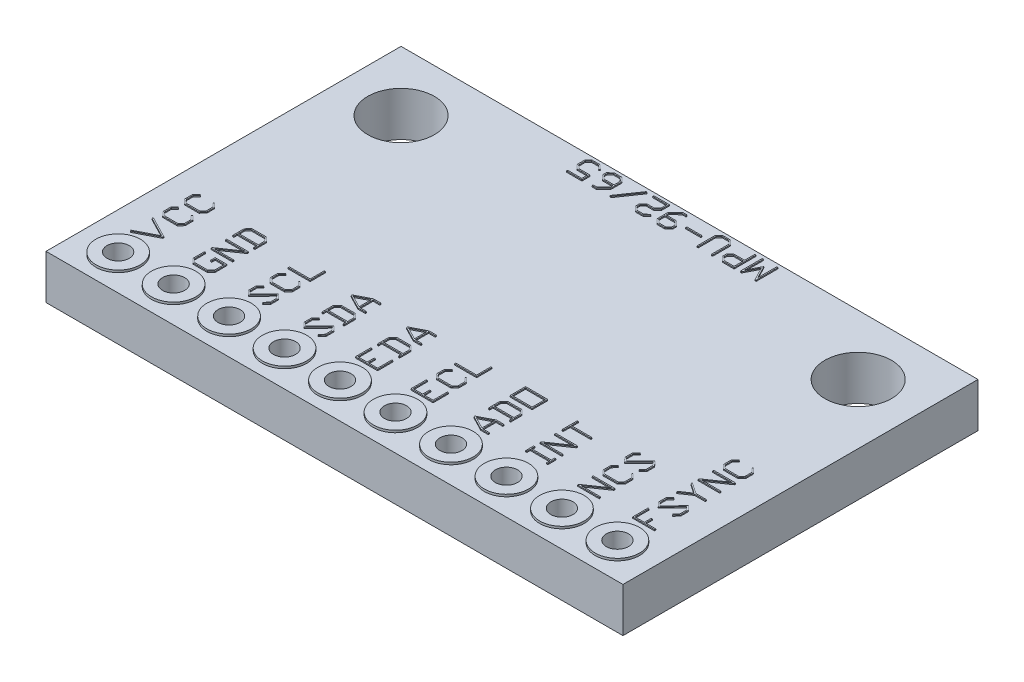
SolidWorks part; units mm, degrees
ref_plane "Alzado" through (0, 0, 0) normal (0, 0, 1) x (1, 0, 0)
ref_plane "Planta" through (0, 0, 0) normal (0, 1, 0) x (1, 0, 0)
ref_plane "Vista lateral" through (0, 0, 0) normal (1, 0, 0) x (0, 0, -1)
sketch "Croquis1" plane through (0, 0, 0) normal (0, 1, 0) x (1, 0, 0)
  line L1 (-13, -8) -> (13, -8)
  line L2 (-13, -8) -> (-13, 8)
  line L3 (-13, 8) -> (13, 8)
  line L4 (13, -8) -> (13, 8)
  line L5 (-13, -8) -> (13, 8) construction
  line L6 (-13, 8) -> (13, -8) construction
  circle A0 centre (-10.3, 5.3) radius 1.5
  circle A1 centre (10.3, 5.3) radius 1.5
  circle A2 centre (11.25, -6.5) radius 0.5
  circle A3 centre (11.25, -6.5) radius 1
  circle A4 centre (8.75, -6.5) radius 0.5
  circle A5 centre (8.75, -6.5) radius 1
  circle A6 centre (6.25, -6.5) radius 0.5
  circle A7 centre (6.25, -6.5) radius 1
  circle A8 centre (3.75, -6.5) radius 0.5
  circle A9 centre (3.75, -6.5) radius 1
  circle A10 centre (1.25, -6.5) radius 0.5
  circle A11 centre (1.25, -6.5) radius 1
  circle A12 centre (-1.25, -6.5) radius 0.5
  circle A13 centre (-1.25, -6.5) radius 1
  circle A14 centre (-3.75, -6.5) radius 0.5
  circle A15 centre (-3.75, -6.5) radius 1
  circle A16 centre (-6.25, -6.5) radius 0.5
  circle A17 centre (-6.25, -6.5) radius 1
  circle A18 centre (-8.75, -6.5) radius 0.5
  circle A19 centre (-8.75, -6.5) radius 1
  circle A20 centre (-11.25, -6.5) radius 0.5
  circle A21 centre (-11.25, -6.5) radius 1
  point P0 (0, 0)
  dimension "D3" = 2.7
  dimension "D7" = 1.5
  dimension "D1" = 26
  dimension "D2" = 16
  dimension "D4" = 2.7
  dimension "D5" = 2.7
  dimension "D6" = 2.7
  dimension "D8" = 1.75
  dimension "D9" = 10
extrude "Saliente-Extruir1" add sketch "Croquis1" against normal blind 2 contours L1 L4 L3 L2 A21 A19 A17 A15 A13 A11 A9 A7 A5 A3 A1 A0 | A3 | A5 | A7 | A9 | A11 | A13 | A15 | A17 | A19 | A21 region at (0, 0, -0.349)
extrude "Cortar-Extruir1" cut sketch "Croquis1<3>" against normal blind 2 contours A20 | A18 | A16 | A14 | A10 | A12 | A8 | A6 | A4 | A2
sketch "Croquis1<3>" plane through (0, 0, 0) normal (0, 1, 0) x (1, 0, 0) same geometry as "Croquis1"
extrude "Saliente-Extruir2" add sketch "Croquis1<4>" along normal blind 0.1 contours A19 A18 | A21 A20 | A17 A16 | A15 A14 | A13 A12 | A11 A10 | A9 A8 | A7 A6 | A5 A4 | A3 A2 region at (10.2783, 0, 6.5) region at (7.7783, 0, 6.5) region at (5.2783, 0, 6.5) region at (2.7783, 0, 6.5) region at (0.2783, 0, 6.5) region at (-2.2217, 0, 6.5) region at (-4.7217, 0, 6.5) region at (-7.2217, 0, 6.5) region at (-9.7217, 0, 6.5) region at (-12.2217, 0, 6.5)
sketch "Croquis1<4>" plane through (0, 0, 0) normal (0, 1, 0) x (1, 0, 0) same geometry as "Croquis1"
sketch "Croquis2" plane through (0, 0, 0) normal (0, 1, 0) x (1, 0, 0)
  line L0 (-10.8805, -5.5708) -> (-10.8805, -2.1435) construction
  line L1 (-8.3805, -5.5708) -> (-8.3805, -2.1435) construction
  line L2 (-5.8805, -5.5708) -> (-5.8805, -2.1435) construction
  line L3 (-3.3805, -5.5708) -> (-3.3805, -2.1435) construction
  line L4 (-0.8805, -5.5708) -> (-0.8805, -2.1435) construction
  line L5 (1.6195, -5.5708) -> (1.6195, -2.1435) construction
  line L6 (4.1195, -5.5708) -> (4.1195, -2.1435) construction
  line L7 (6.6195, -5.5708) -> (6.6195, -2.1435) construction
  line L8 (9.1195, -5.5708) -> (9.1195, -2.1435) construction
  line L9 (11.6195, -5.5708) -> (11.6195, -2.1435) construction
  line L10 (11.6195, -5.5708) -> (11.6195, -0.1979) construction
  circle A0 centre (-11.25, -6.5) radius 1 construction
  text T0 "VCC" font "@Adobe Heiti Std R" height 1
  text T1 "GND" font "@Adobe Heiti Std R" height 1
  text T2 "SCL"
  text T3 "SDA"
  text T4 "EDA"
  text T5 "ECL"
  text T6 "ADO"
  text T7 "INT"
  text T8 "NCS"
  text T9 "FSYNC"
  dimension "D1" = 10
extrude "Saliente-Extruir5" add sketch "Croquis2" along normal blind 0.05
sketch "Croquis6" plane through (0, 0, 0) normal (0, 1, 0) x (1, 0, 0)
  line L8 (12.8, -8) -> (12.8, 7.8)
  line L9 (12.8, 7.8) -> (-13, 7.8)
  line L10 (12.8, -8) -> (12.8, 7.8) construction
  line L11 (12.8, 7.8) -> (-13, 7.8) construction
  text T0 "MPU-92/65" font "@Adobe Heiti Std R" height 1
  dimension "D1" = 0.2
extrude "Saliente-Extruir6" add sketch "Croquis6" along normal blind 0.05
ref_plane "Plano1" through (0, -1, 0) normal (0, -1, 0) x (-1, 0, 0)
mirror "Simetría1" about plane through (0, -1, 0) normal (0, -1, 0) of "Saliente-Extruir2"
